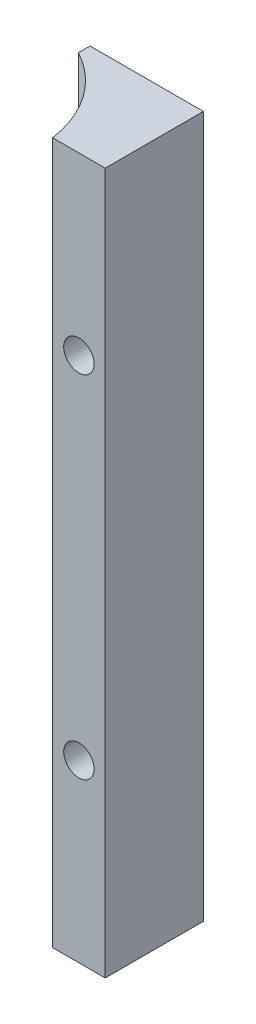
SolidWorks part; units mm, degrees
ref_plane "Front" through (0, 0, 0) normal (0, 0, 1) x (1, 0, 0)
ref_plane "Top" through (0, 0, 0) normal (0, 1, 0) x (1, 0, 0)
ref_plane "Right" through (0, 0, 0) normal (1, 0, 0) x (0, 0, -1)
sketch "Sketch1" plane through (0, 0, 0) normal (0, 1, 0) x (1, 0, 0)
  line L0 (0, 0) -> (0, 8.4)
  line L1 (0, 8.4) -> (-9.6948, 8.4)
  line L2 (-9.6948, 8.4) -> (-9.6948, 7.4)
  line L3 (-4.5, 0) -> (0, 0)
  arc A0 (-9.6948, 7.4) -> (-4.5, 0) centre (-14.3979, -1.425) cw
  dimension "D3" = 10
  dimension "D1" = 4.5
  dimension "D2" = 8.4
  dimension "D4" = 1.425
  dimension "D5" = 1
extrude "Boss-Extrude1" add sketch "Sketch1" along normal blind 60
sketch "Sketch2" plane through (0, 0, 0) normal (0, 0, 1) x (1, 0, 0)
  line L0 (-2.25, 60) -> (-2.25, 0) construction
  line L1 (-4.5, 60) -> (0, 60) construction
  line L2 (-4.5, 0) -> (0, 0) construction
  line L4 (-4.5, 60) -> (-4.5, 0) construction
  point P6 (-2.25, 45)
  point P7 (-2.25, 15)
  dimension "D1" = 15
  dimension "D2" = 15
  dimension "D3" = 2.25
hole_wizard "Ø2.6 (2.6) Diameter Hole1" positions "3DSketch1" profile "Sketch3" hole size "Ø2.6" standard "ANSI Metric" end condition up to next
sketch3d "3DSketch1"
  point P0 (-2.25, 45, 0)
  point P3 (-2.25, 15, 0)
sketch "Sketch3" plane through (-2.25, 45, 0) normal (1, 0, 0) x (0, -1, 0)
  line L0 (0, 0) -> (0, 8.4)
  line L1 (0, 8.4) -> (1.3, 8.4)
  line L2 (1.3, 8.4) -> (1.3, 0)
  line L5 (1.3, 0) -> (0, 0)
  line L11 (0, -6.35) -> (0, 107.95) construction
  dimension "Thru Hole Dia." = 2.6
  dimension "Thru Hole Depth" = 8.4
